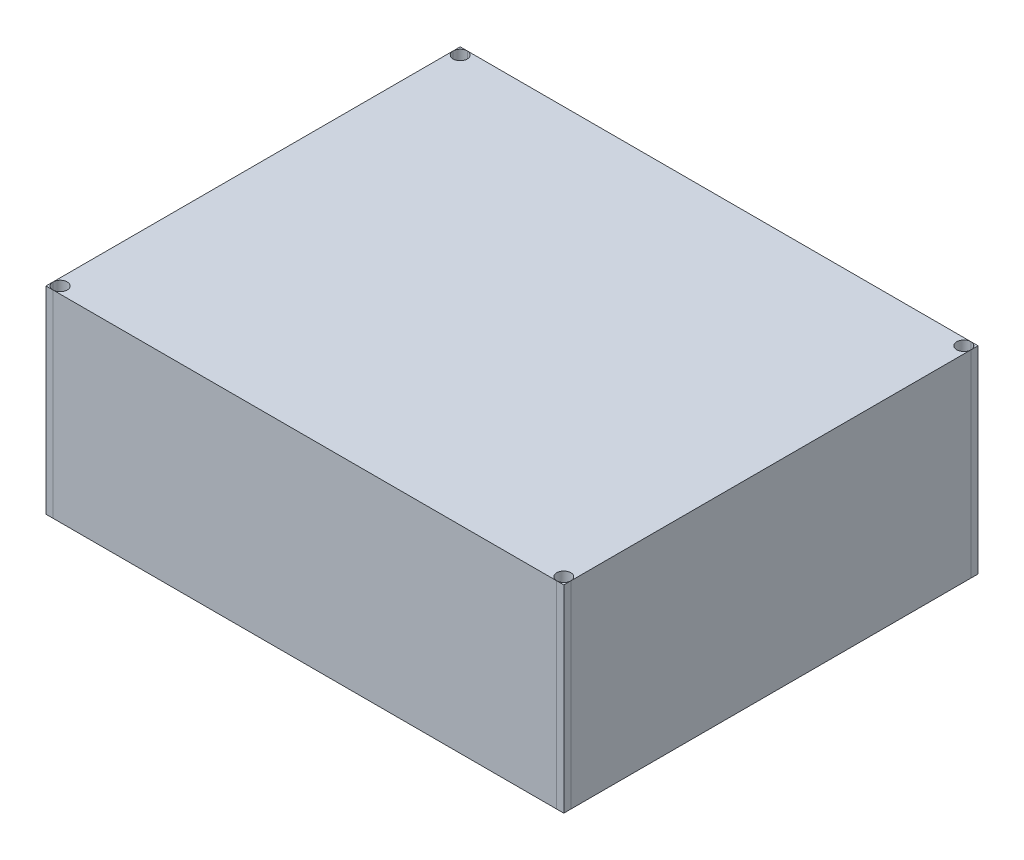
SolidWorks part; units mm, degrees
ref_plane "前基準面" through (0, 0, 0) normal (0, 0, 1) x (1, 0, 0)
ref_plane "上基準面" through (0, 0, 0) normal (0, 1, 0) x (1, 0, 0)
ref_plane "右基準面" through (0, 0, 0) normal (1, 0, 0) x (0, 0, -1)
sketch "草圖1" plane through (0, 0, 0) normal (0, 1, 0) x (1, 0, 0)
  line L1 (55, 44) -> (-55, 44)
  line L2 (55, 44) -> (55, -44)
  line L3 (55, -44) -> (-55, -44)
  line L4 (-55, 44) -> (-55, -44)
  line L5 (0, -44) -> (0, 44) construction
  line L6 (55, 0) -> (-55, 0) construction
  circle A0 centre (-53.5, -42.5) radius 1.5 construction
  circle A1 centre (-53.5, 42.5) radius 1.5 construction
  circle A2 centre (53.5, 42.5) radius 1.5 construction
  circle A3 centre (53.5, -42.5) radius 1.5 construction
  point P0 (0, 0)
  dimension "D3" = 3
  dimension "D1" = 110
  dimension "D2" = 88
extrude "填料-伸長1" add sketch "草圖1" along normal blind 42
sketch "草圖3" plane through (0, 42, 0) normal (0, 1, 0) x (1, 0, 0)
  circle A0 centre (53.5, -42.5) radius 1.5 construction
  circle A1 centre (53.5, 42.5) radius 1.5 construction
  circle A2 centre (-53.5, 42.5) radius 1.5 construction
  circle A3 centre (-53.5, -42.5) radius 1.5 construction
  circle A4 centre (53.5, -42.5) radius 1.5
  circle A5 centre (53.5, 42.5) radius 1.5
  circle A6 centre (-53.5, 42.5) radius 1.5
  circle A7 centre (-53.5, -42.5) radius 1.5
extrude "除料-伸長1" cut sketch "草圖3" against normal through all
